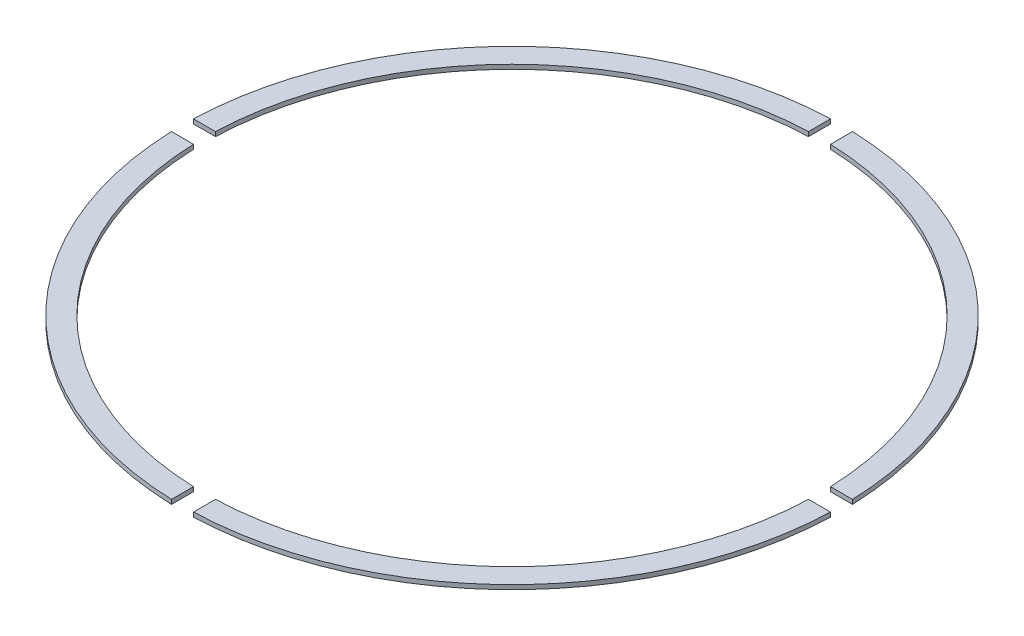
SolidWorks part; units mm, degrees
ref_plane "Front Plane" through (0, 0, 0) normal (0, 0, 1) x (1, 0, 0)
ref_plane "Top Plane" through (0, 0, 0) normal (0, 1, 0) x (1, 0, 0)
ref_plane "Right Plane" through (0, 0, 0) normal (1, 0, 0) x (0, 0, -1)
sketch "Sketch1" plane through (0, 0, 0) normal (0, 1, 0) x (1, 0, 0)
  line L0 (-210, 0) -> (210, 0) construction
  circle A0 centre (0, 0) radius 210
  circle A1 centre (0, 0) radius 225
  dimension "D1" = 420
  dimension "D2" = 450
extrude "Boss-Extrude1" add sketch "Sketch1" along normal mid plane 3
sketch "Sketch3" plane through (0, 0, 0) normal (1, 0, 0) x (0, 0, -1)
  line L0 (0, 175.2321) -> (0, -208.5549) construction
sketch "Sketch2" plane through (0, 0, 0) normal (0, 1, 0) x (1, 0, 0)
  line L1 (189.3497, 7.5) -> (245.6503, 7.5)
  line L2 (189.3497, 7.5) -> (189.3497, -7.5)
  line L3 (189.3497, -7.5) -> (245.6503, -7.5)
  line L4 (245.6503, 7.5) -> (245.6503, -7.5)
  line L5 (189.3497, 7.5) -> (245.6503, -7.5) construction
  line L6 (189.3497, -7.5) -> (245.6503, 7.5) construction
  circle A0 centre (0, 0) radius 217.5 construction
  circle A1 centre (0, 0) radius 210 construction
  point P5 (217.5, 0)
  dimension "D1" = 7.5
  dimension "D2" = 15
extrude "Cut-Extrude1" cut sketch "Sketch2" against normal through all both and the other way through all
pattern_circular "CirPattern1" count 4 every 90 about axis through (0, 175.2321, 0) along (0, -1, 0) of "Cut-Extrude1"
